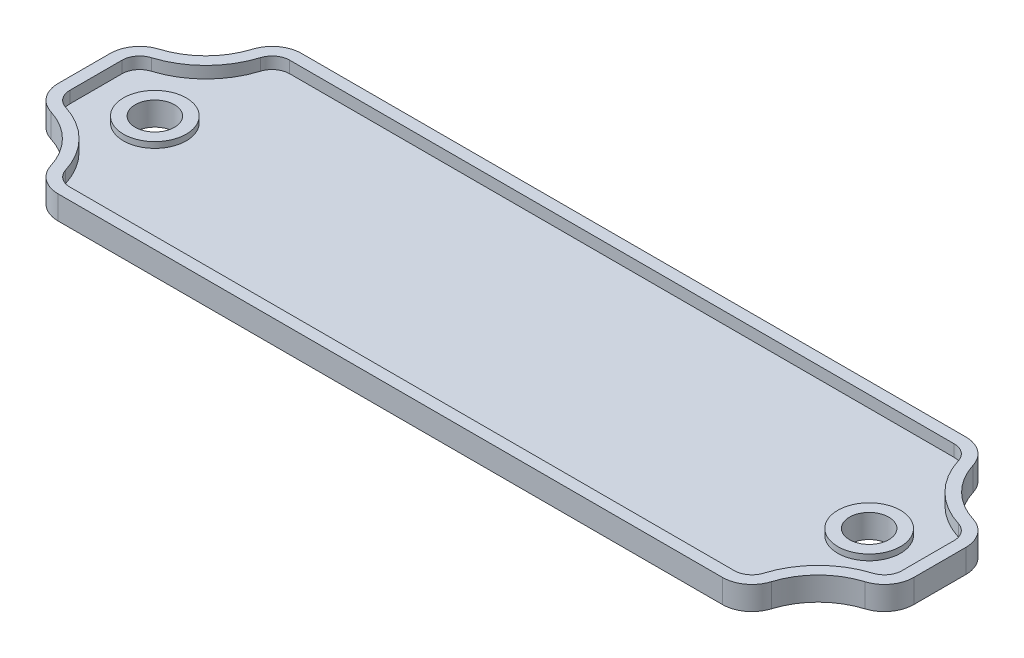
SolidWorks part; units mm, degrees
ref_plane "Front Plane" through (0, 0, 0) normal (0, 0, 1) x (1, 0, 0)
ref_plane "Top Plane" through (0, 0, 0) normal (0, 1, 0) x (1, 0, 0)
ref_plane "Right Plane" through (0, 0, 0) normal (1, 0, 0) x (0, 0, -1)
sketch "Sketch2" plane through (0, 0, 0) normal (0, 1, 0) x (1, 0, 0)
  line L0 (-84.3884, 0) -> (94.8556, 0) construction
  line L1 (-42.3139, 15.5) -> (42.3139, 15.5)
  line L2 (54.5, 3.3139) -> (54.5, -3.3139)
  line L3 (0, 28.6741) -> (0, -37.251) construction
  line L4 (-42.3139, -15.5) -> (42.3139, -15.5)
  line L5 (-54.5, 3.3139) -> (-54.5, -3.3139)
  line L6 (-42.3139, 14) -> (42.3139, 14)
  line L7 (53, 3.3139) -> (53, -3.3139)
  line L8 (-42.3139, -14) -> (42.3139, -14)
  line L9 (-53, 3.3139) -> (-53, -3.3139)
  circle A0 centre (-45.5, 0) radius 2.5
  circle A1 centre (45.5, 0) radius 2.5
  circle A2 centre (-45.5, 0) radius 4
  circle A3 centre (45.5, 0) radius 4
  arc A4 (45.8981, 12.8529) -> (51.8529, 6.8981) centre (54.5, 15.5) ccw
  arc A5 (45.8981, 12.8529) -> (42.3139, 15.5) centre (42.3139, 11.75) ccw
  arc A6 (51.8529, 6.8981) -> (54.5, 3.3139) centre (50.75, 3.3139) cw
  arc A7 (51.8529, -6.8981) -> (54.5, -3.3139) centre (50.75, -3.3139) ccw
  arc A8 (45.8981, -12.8529) -> (51.8529, -6.8981) centre (54.5, -15.5) cw
  arc A9 (45.8981, -12.8529) -> (42.3139, -15.5) centre (42.3139, -11.75) cw
  arc A10 (-45.8981, -12.8529) -> (-42.3139, -15.5) centre (-42.3139, -11.75) ccw
  arc A11 (-45.8981, -12.8529) -> (-51.8529, -6.8981) centre (-54.5, -15.5) ccw
  arc A12 (-51.8529, -6.8981) -> (-54.5, -3.3139) centre (-50.75, -3.3139) cw
  arc A13 (-51.8529, 6.8981) -> (-54.5, 3.3139) centre (-50.75, 3.3139) ccw
  arc A14 (-45.8981, 12.8529) -> (-51.8529, 6.8981) centre (-54.5, 15.5) cw
  arc A15 (-45.8981, 12.8529) -> (-42.3139, 15.5) centre (-42.3139, 11.75) cw
  arc A16 (44.4644, 12.4118) -> (42.3139, 14) centre (42.3139, 11.75) ccw
  arc A17 (44.4644, 12.4118) -> (51.4118, 5.4644) centre (54.5, 15.5) ccw
  arc A18 (51.4118, 5.4644) -> (53, 3.3139) centre (50.75, 3.3139) cw
  arc A19 (51.4118, -5.4644) -> (53, -3.3139) centre (50.75, -3.3139) ccw
  arc A20 (44.4644, -12.4118) -> (51.4118, -5.4644) centre (54.5, -15.5) cw
  arc A21 (44.4644, -12.4118) -> (42.3139, -14) centre (42.3139, -11.75) cw
  arc A22 (-44.4644, -12.4118) -> (-42.3139, -14) centre (-42.3139, -11.75) ccw
  arc A23 (-44.4644, -12.4118) -> (-51.4118, -5.4644) centre (-54.5, -15.5) ccw
  arc A24 (-51.4118, -5.4644) -> (-53, -3.3139) centre (-50.75, -3.3139) cw
  arc A25 (-51.4118, 5.4644) -> (-53, 3.3139) centre (-50.75, 3.3139) ccw
  arc A26 (-44.4644, 12.4118) -> (-51.4118, 5.4644) centre (-54.5, 15.5) cw
  arc A27 (-44.4644, 12.4118) -> (-42.3139, 14) centre (-42.3139, 11.75) cw
  point P21 (54.5, 0)
  point P29 (0, -15.5)
  point P42 (0, 15.5)
  dimension "D1" = 5
  dimension "D2" = 5
  dimension "D4" = 8
  dimension "D5" = 8
  dimension "D7" = 9
  dimension "D8" = 9
  dimension "D10" = 3.75
  dimension "D11" = 3.75
  dimension "D3" = 91
  dimension "D6" = 15.5
  dimension "D9" = 54.5
  dimension "D12" = 1.5
extrude "Boss-Extrude1" add sketch "Sketch2" against normal blind 0.75 contours A2 A0 region at (-49.3869, 0, 0)
extrude "Boss-Extrude2" add sketch "Sketch2<4>" against normal blind 0.75 separate body contours A3 A1 region at (41.6131, 0, 0)
sketch "Sketch2<4>" plane through (0, 0, 0) normal (0, 1, 0) x (1, 0, 0) same geometry as "Sketch2"
extrude "Boss-Extrude3" add sketch "Sketch2<5>" along normal blind 3 separate body contours A15 A14 A13 L5 A12 A11 A10 L4 A9 A8 A7 L2 A6 A4 A5 L1 A26 A27 L6 A16 A17 A18 L7 A19 A20 A21 L8 A22 A23 A24 L9 A25 region at (0, 0, -14.3668)
sketch "Sketch2<5>" plane through (0, 0, 0) normal (0, 1, 0) x (1, 0, 0) same geometry as "Sketch2"
extrude "Boss-Extrude4" add sketch "Sketch2<6>" along normal blind 1.5 contours A27 A26 A25 L9 A24 A23 A22 L8 A21 A20 A19 L7 A18 A17 A16 L6 A3 A2 region at (0, 0, 0)
sketch "Sketch2<6>" plane through (0, 0, 0) normal (0, 1, 0) x (1, 0, 0) same geometry as "Sketch2"
extrude "Boss-Extrude5" add sketch "Sketch2<7>" along normal blind 2.25 contours A2 A0 region at (-49.3869, 0, 0)
sketch "Sketch2<7>" plane through (0, 0, 0) normal (0, 1, 0) x (1, 0, 0) same geometry as "Sketch2"
extrude "Boss-Extrude6" add sketch "Sketch2<8>" along normal blind 2.25 contours A3 A1 region at (41.6131, 0, 0)
sketch "Sketch2<8>" plane through (0, 0, 0) normal (0, 1, 0) x (1, 0, 0) same geometry as "Sketch2"
